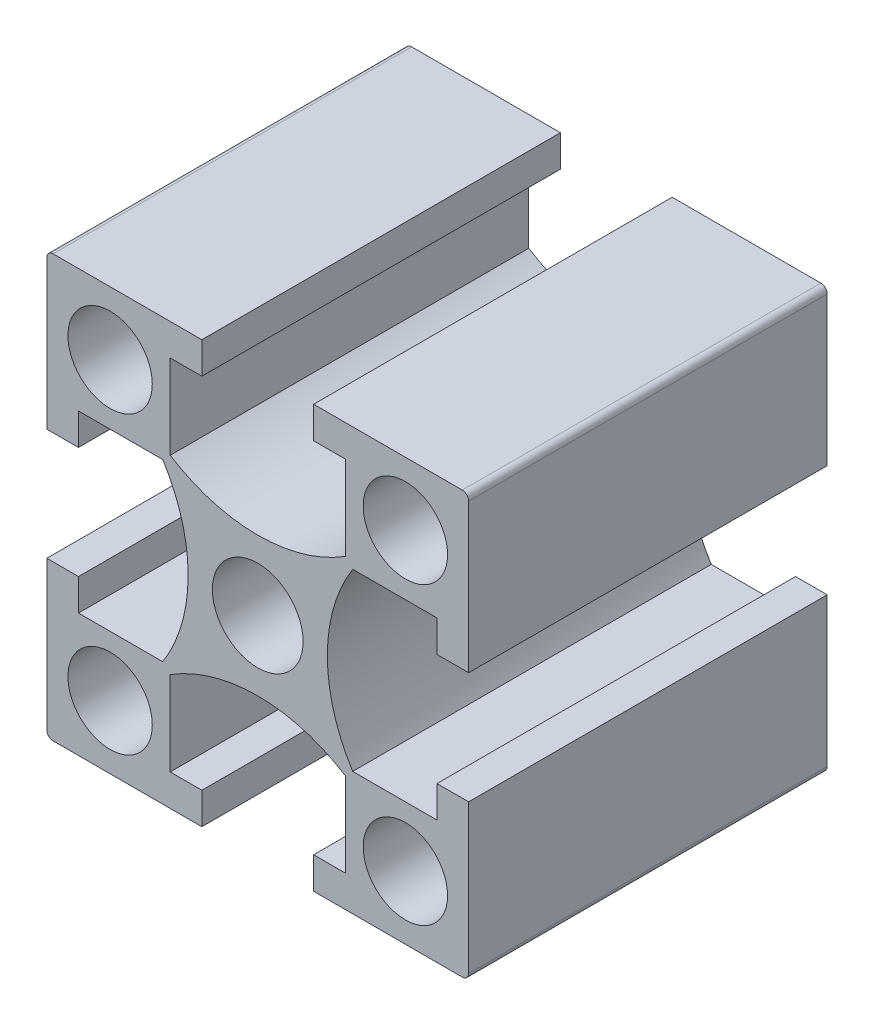
SolidWorks part; units mm, degrees
material "3.0255 (EN-AW 1350A)"
ref_plane "정면" through (0, 0, 0) normal (0, 0, 1) x (1, 0, 0)
ref_plane "윗면" through (0, 0, 0) normal (0, 1, 0) x (1, 0, 0)
ref_plane "우측면" through (0, 0, 0) normal (1, 0, 0) x (0, 0, -1)
sketch "스케치1" plane through (0, 0, 0) normal (0, 0, 1) x (1, 0, 0)
  line L0 (0, 32.0265) -> (0, -31.6588) construction
  line L1 (-10, 10) -> (-10, -10)
  line L2 (-10, 10) -> (10, 10)
  line L3 (-10, 2.65) -> (-8.5, 2.65)
  line L4 (13.6618, 0) -> (-11.6993, 0) construction
  line L5 (-8.5, 2.65) -> (-8.5, 4.15)
  line L6 (-8.5, 4.15) -> (-4.5032, 4.15)
  line L7 (-10, -2.65) -> (-8.5, -2.65)
  line L8 (-8.5, -2.65) -> (-8.5, -4.15)
  line L9 (-8.5, -4.15) -> (-4.5032, -4.15)
  line L10 (-10, -10) -> (10, -10)
  line L11 (10, 10) -> (10, -10)
  circle A0 centre (-7, 7) radius 2
  circle A1 centre (-7, -7) radius 2
  arc A2 (-4.5032, 4.15) -> (-4.5032, -4.15) centre (-11.0587, 0) cw
  circle A3 centre (0, 0) radius 2.15
  circle A4 centre (7, 7) radius 2
  circle A5 centre (7, -7) radius 2
  point P21 (-10, 0)
  point P23 (-3.3, 0)
  point P31 (0, -10)
  point P32 (0, 10)
  dimension "D3" = 4
  dimension "D9" = 6.7
  dimension "D10" = 4.3
  dimension "D11" = 7.7587
  dimension "D1" = 20
  dimension "D2" = 20
  dimension "D4" = 14
  dimension "D5" = 14
  dimension "D6" = 5.3
  dimension "D7" = 8.3
  dimension "D8" = 1.5
extrude "보스-돌출1" add sketch "스케치1" along normal blind 17 contours A0 | A4 | A3 | A5 | A1 | A2 L6 L5 L3 L1 L7 L8 L9 | L2 L11 L10 L1 region at (-6.6069, 0, 0) region at (-7, 7, 0) region at (-7, -7, 0) region at (0, 0, 0) region at (7, 7, 0) region at (7, -7, 0)
extrude "컷-돌출1" cut sketch "스케치1<3>" along normal up to next contours A2 L6 L5 L3 L1 L7 L8 L9 region at (-6.6069, 0, 0)
sketch "스케치1<3>" plane through (0, 0, 0) normal (0, 0, 1) x (1, 0, 0) same geometry as "스케치1"
pattern_circular "원형 패턴1" count 4 over 360 about axis through (0, 0, 17) along (0, 0, -1) of "컷-돌출1" reverse direction yes
fillet "필렛1" radius 0.3 4 edges at (10, -10, 8.5) (-10, -10, 8.5) (-10, 10, 8.5) (10, 10, 8.5)
sketch "스케치2" plane through (0, 0, 0) normal (1, 0, 0) x (0, 0, -1)
  line L0 (3.7612, 0) -> (-18.9549, 0) construction
  line L1 (-8.5, 34.3807) -> (-8.5, -14.9807) construction
  line L4 (0, 9.7) -> (0, 2.65) construction
  line L5 (0, 9.7) -> (-17, 9.7) construction
  line L6 (0, 9.7) -> (-17, 9.7) construction
  circle A0 centre (-8.5, 0) radius 2.5
  point P6 (-8.5, 9.7)
  dimension "D1" = 5
  dimension "D2" = 8.5
extrude "컷-돌출2" cut sketch "스케치2" against normal through all both and the other way through all contours A0
